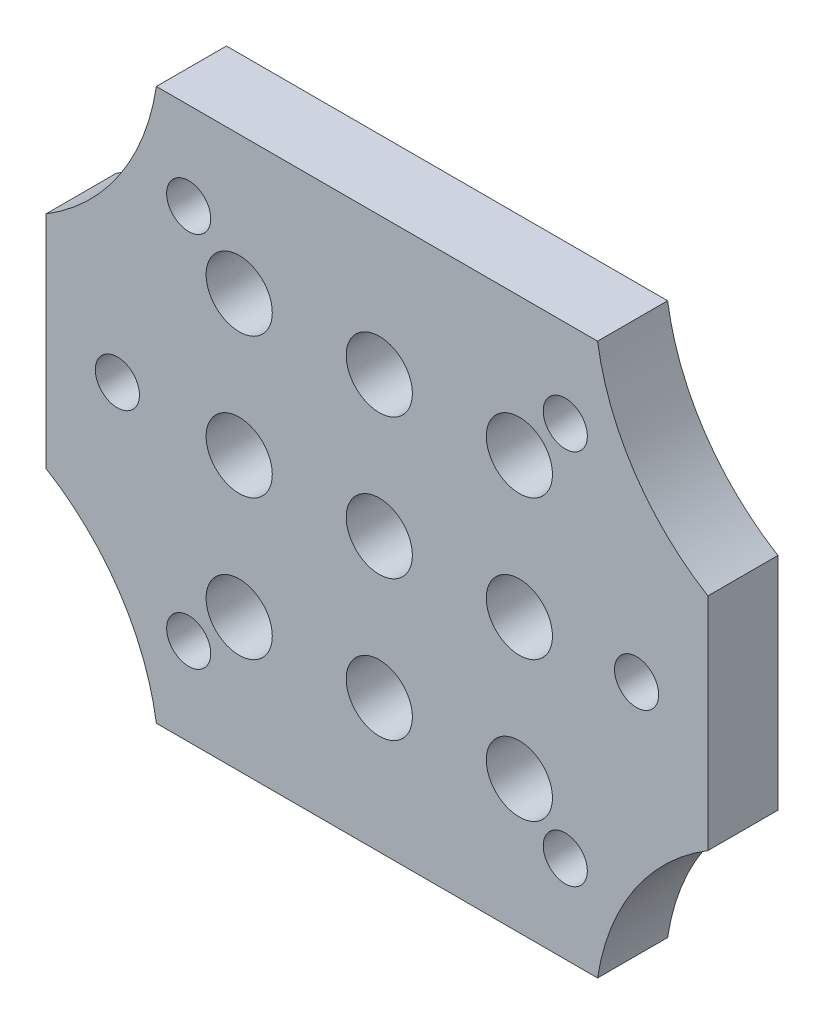
SolidWorks part; units mm, degrees
material "Custom Plastic"
ref_plane "X-Y Datum" through (0, 0, 0) normal (0, 0, 1) x (1, 0, 0)
ref_plane "X-Z Datum" through (0, 0, 0) normal (0, 1, 0) x (1, 0, 0)
ref_plane "Y-Z Datum" through (0, 0, 0) normal (1, 0, 0) x (0, 0, -1)
sketch "Sketch1" plane through (0, 0, 0) normal (0, 0, 1) x (1, 0, 0)
  line L1 (-30, -25) -> (30, -25)
  line L2 (-30, -25) -> (-30, 25)
  line L3 (-30, 25) -> (30, 25)
  line L4 (30, -25) -> (30, 25)
  line L5 (-30, -25) -> (30, 25) construction
  line L6 (-30, 25) -> (30, -25) construction
  point P0 (0, 0)
  dimension "D1" = 60
  dimension "D2" = 50
extrude "Boss-Extrude1" add sketch "Sketch1" along normal blind 6.35
sketch "Sketch2" plane through (0, 0, 6.35) normal (0, 0, 1) x (1, 0, 0)
  line L0 (-30, 0) -> (-17.0711, 0) construction
  line L1 (-17.0711, -17.0711) -> (17.0711, -17.0711) construction
  line L2 (-17.0711, -17.0711) -> (-17.0711, 17.0711) construction
  line L3 (-17.0711, 17.0711) -> (17.0711, 17.0711) construction
  line L4 (17.0711, -17.0711) -> (17.0711, 17.0711) construction
  line L5 (-17.0711, -17.0711) -> (17.0711, 17.0711) construction
  line L6 (-17.0711, 17.0711) -> (17.0711, -17.0711) construction
  line L7 (-30, 25) -> (-30, -25) construction
  line L8 (17.0711, 0) -> (30, 0) construction
  line L9 (30, -25) -> (30, 25) construction
  line L10 (-30, 0) -> (-30, 10) construction
  line L11 (0, 17.0711) -> (0, 25) construction
  line L12 (30, 25) -> (-30, 25) construction
  line L13 (0, 25) -> (-20, 25) construction
  line L15 (0, -43.0151) -> (0, 43.0151) construction
  line L16 (55.1739, 0) -> (-55.1739, 0) construction
  circle A0 centre (-17.0711, 17.0711) radius 2
  circle A1 centre (17.0711, 17.0711) radius 2
  circle A2 centre (-17.0711, -17.0711) radius 2
  circle A3 centre (17.0711, -17.0711) radius 2
  circle A4 centre (-23.5355, 0) radius 2
  circle A5 centre (23.5355, 0) radius 2
  arc A6 (-30, 10) -> (-20, 25) centre (-41.0638, 28.2092) ccw
  arc A7 (30, 10) -> (20, 25) centre (41.0638, 28.2092) cw
  arc A8 (-30, -10) -> (-20, -25) centre (-41.0638, -28.2092) cw
  arc A9 (30, -10) -> (20, -25) centre (41.0638, -28.2092) ccw
  point P0 (0, 0)
  line M3 (30, -25) -> (30, 25)
  line M4 (30, 25) -> (-30, 25)
  line M5 (-30, 25) -> (-30, -25)
  line M6 (-30, -25) -> (30, -25)
  dimension "D1" = 4
  dimension "D2" = 4
  dimension "D3" = 10
  dimension "D4" = 20
extrude "Cut-Extrude1" cut sketch "Sketch2" against normal blind 6.35 contours A6 M5 M4 | A8 M5 M6 | A9 M3 M6 | A7 M3 M4 | A1 | A5 | A3 | A2 | A4 | A0 region at (-17.0711, 17.0711, 6.35) region at (17.0711, 17.0711, 6.35) region at (-17.0711, -17.0711, 6.35) region at (17.0711, -17.0711, 6.35) region at (-23.5355, 0, 6.35) region at (23.5355, 0, 6.35) region at (-26.0956, 19.2796, 6.35) region at (-26.0956, -19.2796, 6.35) region at (26.0956, 19.2796, 6.35) region at (26.0956, -19.2796, 6.35)
sketch "Sketch3" plane through (0, 0, 6.35) normal (0, 0, 1) x (1, 0, 0)
  line L0 (-17.0711, 17.0711) -> (17.0711, -17.0711) construction
  circle A0 centre (-12.4909, 12.4909) radius 3
extrude "Cut-Extrude2" cut sketch "Sketch3" against normal through all
pattern_linear "LPattern1" count 3 spacing 12.7 along (1, 0, 0) of "Cut-Extrude2"
pattern_linear "LPattern2" count 3 spacing 12.7 along (0, -1, 0) of "LPattern1"
